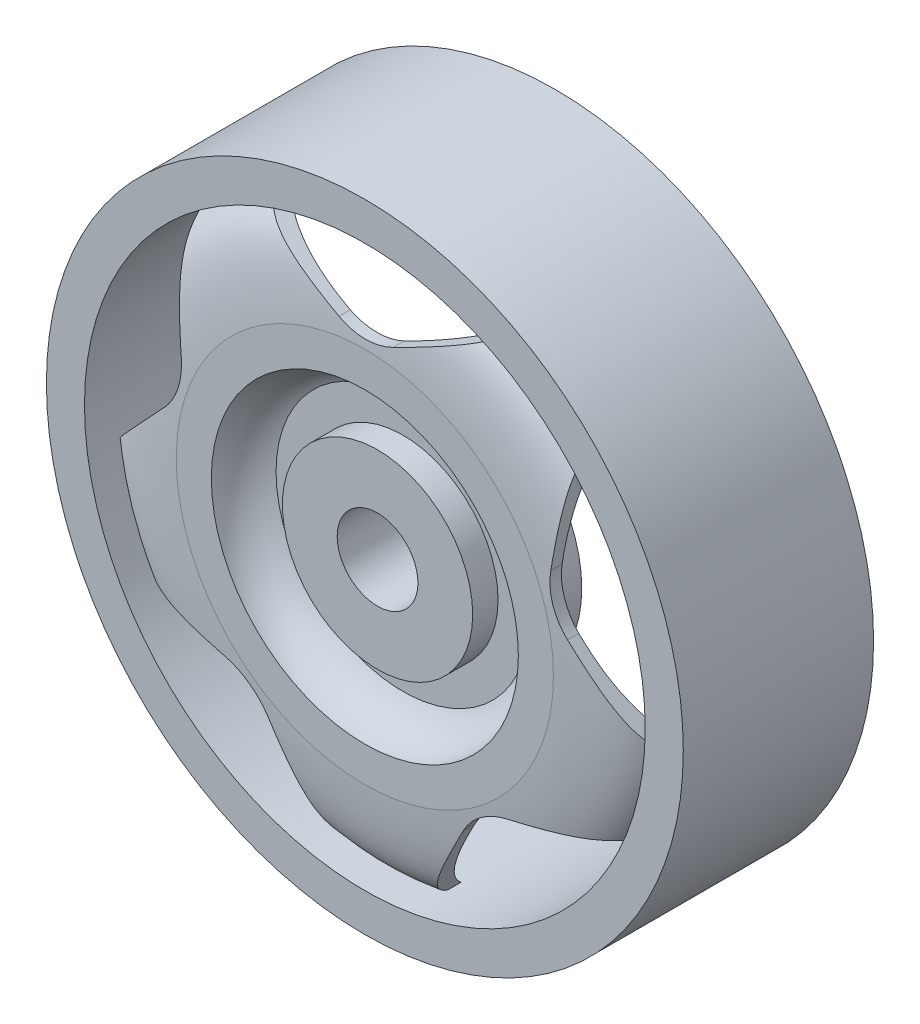
SolidWorks part; units mm, degrees
ref_plane "Front Plane" through (0, 0, 0) normal (0, 0, 1) x (1, 0, 0)
ref_plane "Top Plane" through (0, 0, 0) normal (0, 1, 0) x (1, 0, 0)
ref_plane "Right Plane" through (0, 0, 0) normal (1, 0, 0) x (0, 0, -1)
sketch "Sketch1" plane through (0, 0, 0) normal (1, 0, 0) x (0, 0, -1)
  line L0 (-0.0107, 12.1) -> (-0.0107, 14.8643)
  line L1 (-0.0107, 25.1) -> (24.9893, 25.1)
  line L2 (-0.0107, 22.1) -> (2.9893, 22.1)
  line L3 (2.9893, 10) -> (2.9893, 7.5)
  line L4 (2.9893, 7.5) -> (0.9893, 7.5)
  line L5 (0.9893, 7.5) -> (0.9893, 0)
  line L6 (-13.2759, 0) -> (14.215, 0) construction
  line L7 (-0.0107, 22.1) -> (-0.0107, 25.1)
  line L8 (24.9893, 25.1) -> (24.9893, 22.1)
  line L9 (24.9893, 22.1) -> (4.0868, 22.1)
  line L10 (0.9893, 14.8643) -> (0.9893, 12.992)
  line L11 (4.0868, 10) -> (8.0868, 10)
  line L12 (8.0868, 10) -> (8.0868, 0)
  line L13 (8.0868, 0) -> (0.9893, 0)
  arc A0 (-0.0107, 12.1) -> (2.9893, 10) centre (-0.3983, 8.3534) cw
  arc A1 (4.0868, 22.1) -> (0.9893, 14.8643) centre (9.2266, 15.6189) ccw
  arc A2 (0.9893, 12.992) -> (4.0868, 10) centre (-0.1123, 8.7522) cw
  spline S0 degree 3 poles (2.9893, 22.1) (1.2339, 21.0874) (0.2751, 20.019) (-0.0107, 14.8643) knots 0 0 0 0 1 1 1 1
  point P6 (3, 12)
  dimension "D5" = 2.2559
  dimension "D2" = 25
  dimension "D3" = 3
  dimension "D4" = 3
  dimension "D6" = 2
  dimension "D7" = 2.5
  dimension "D8" = 2
  dimension "D9" = 13
  dimension "D10" = 1
  dimension "D11" = 1
  dimension "D12" = 4
revolve "Revolve1" add sketch "Sketch1" angle 360 about L6
sketch "Sketch2" plane through (0, 0, 0.0107) normal (0, 0, 1) x (1, 0, 0)
  line L0 (0, 22.1) -> (0, 0) construction
  line L1 (-10, 19.7081) -> (-2.1298, 16.0027)
  line L2 (2.1298, 16.0027) -> (10, 19.7081)
  line L3 (15.6534, 15.6007) -> (14.5614, 6.9707)
  line L4 (15.8777, 2.9195) -> (21.8337, -3.4204)
  line L5 (19.6743, -10.0664) -> (11.1292, -11.6946)
  line L6 (7.6831, -14.1984) -> (3.494, -21.8221)
  line L7 (-3.494, -21.8221) -> (-7.6831, -14.1984)
  line L8 (-11.1292, -11.6946) -> (-19.6743, -10.0664)
  line L9 (-21.8337, -3.4204) -> (-15.8777, 2.9195)
  line L10 (-14.5614, 6.9707) -> (-15.6534, 15.6007)
  circle A0 centre (0, 0) radius 22.1 construction
  circle A1 centre (0, 0) radius 22.1 construction
  arc A2 (-2.1298, 16.0027) -> (2.1298, 16.0027) centre (0, 20.5264) ccw
  arc A3 (10, 19.7081) -> (-10, 19.7081) centre (0, 0) ccw
  arc A4 (14.5614, 6.9707) -> (15.8777, 2.9195) centre (19.5218, 6.343) ccw
  arc A5 (21.8337, -3.4204) -> (15.6534, 15.6007) centre (0, 0) ccw
  arc A6 (11.1292, -11.6946) -> (7.6831, -14.1984) centre (12.0651, -16.6062) ccw
  arc A7 (3.494, -21.8221) -> (19.6743, -10.0664) centre (0, 0) ccw
  arc A8 (-7.6831, -14.1984) -> (-11.1292, -11.6946) centre (-12.0651, -16.6062) ccw
  arc A9 (-19.6743, -10.0664) -> (-3.494, -21.8221) centre (0, 0) ccw
  arc A10 (-15.8777, 2.9195) -> (-14.5614, 6.9707) centre (-19.5218, 6.343) ccw
  arc A11 (-15.6534, 15.6007) -> (-21.8337, -3.4204) centre (0, 0) ccw
  point P12 (0, 15)
  point P35 (0, 0)
  dimension "D3" = 5
  dimension "D1" = 10
  dimension "D2" = 15
  dimension "D4" = 5
extrude "Cut-Extrude1" cut sketch "Sketch2" against normal blind 10
sketch "Sketch3" plane through (0, 0, -8.0868) normal (0, 0, -1) x (-1, 0, 0)
  circle A0 centre (0, 0) radius 6
  dimension "D1" = 12
extrude "Boss-Extrude1" add sketch "Sketch3" along normal blind 25
sketch "Sketch4" plane through (0, 0, -33.0868) normal (0, 0, -1) x (-1, 0, 0)
  line L0 (-2.5475, 2.4) -> (2.5475, 2.4)
  line L1 (-3.5, 0) -> (3.5, 0) construction
  line L2 (-2.5475, -2.4) -> (2.5475, -2.4)
  arc A0 (-2.5475, 2.4) -> (-2.5475, -2.4) centre (0, 0) ccw
  arc A1 (2.5475, -2.4) -> (2.5475, 2.4) centre (0, 0) ccw
  dimension "D1" = 7
  dimension "D2" = 2.4
extrude "Cut-Extrude2" cut sketch "Sketch4" against normal blind 12
sketch "Sketch5" plane through (0, 0, 0) normal (1, 0, 0) x (0, 0, -1)
  line L1 (-0.0107, 25.1) -> (-0.0107, -25.1) construction
  line L2 (24.9893, -25.1) -> (24.9893, 25.1) construction
  line L3 (12.4893, 21.6) -> (12.4893, 27) construction
  line L4 (0, 0) -> (33.0868, 0) construction
  line L5 (33.0868, -2.4) -> (33.0868, 2.4) construction
  line L6 (-0.0107, 14.6) -> (-0.0107, 24.9185)
  line L7 (-0.0107, 24.9185) -> (24.9893, 25.1)
  line L8 (24.9893, 25.1) -> (24.9893, 14.6)
  arc A0 (12.4893, 21.6) -> (0.6779, 20.7166) centre (11.5988, -45.8941) ccw
  arc A1 (-0.1468, 19.8936) -> (-0.0107, 14.6) centre (13.6641, 17.6) ccw
  arc A2 (-0.1468, 19.8936) -> (0.6779, 20.7166) centre (0.8397, 19.7297) cw
  arc A3 (25.1253, 19.8936) -> (24.9893, 14.6) centre (11.3145, 17.6) cw
  arc A4 (25.1253, 19.8936) -> (24.3006, 20.7166) centre (24.1389, 19.7297) ccw
  arc A5 (12.4893, 21.6) -> (24.3006, 20.7166) centre (13.3798, -45.8941) cw
  point P6 (12.4893, 21.6)
  point P7 (-0.0107, 20.6)
  point P8 (12.4893, 31.1)
  point P21 (-0.0107, 20.6)
  dimension "D3" = 67.5
  dimension "D4" = 14
  dimension "D5" = 1
  dimension "D2" = 6
  dimension "D6" = 21.6
revolve "Revolve2" add sketch "Sketch5" angle 360 about L4 rebuild error yes other way angle 360
sketch "Croquis2" plane through (0, 0, -24.9893) normal (0, 0, -1) x (-1, 0, 0)
  circle A0 centre (0, 0) radius 22.1
  circle A1 centre (0, 0) radius 25.1
extrude "Cortar-Extruir2" cut sketch "Croquis2" against normal blind 10
sketch "Croquis3" plane through (0, 0, -33.0868) normal (0, 0, -1) x (-1, 0, 0)
  circle A1 centre (0, 0) radius 6
  circle A2 centre (0, 0) radius 6
  dimension "D1" = 0
extrude "Cortar-Extruir3" cut sketch "Croquis3" against normal blind 26
sketch "Croquis5" plane through (0, 0, -8.0868) normal (0, 0, -1) x (-1, 0, 0)
  circle A1 centre (0, 0) radius 10
  circle A2 centre (0, 0) radius 10
  dimension "D1" = 0
extrude "Cortar-Extruir4" cut sketch "Croquis5" against normal up to surface (1 mm away) up to face at (-6, 0, -7.0868)
sketch "Croquis6" plane through (0, 0, -7.0868) normal (0, 0, -1) x (-1, 0, 0)
  circle A0 centre (0, 0) radius 3.1817
extrude "Cortar-Extruir5" cut sketch "Croquis6" against normal blind 26
